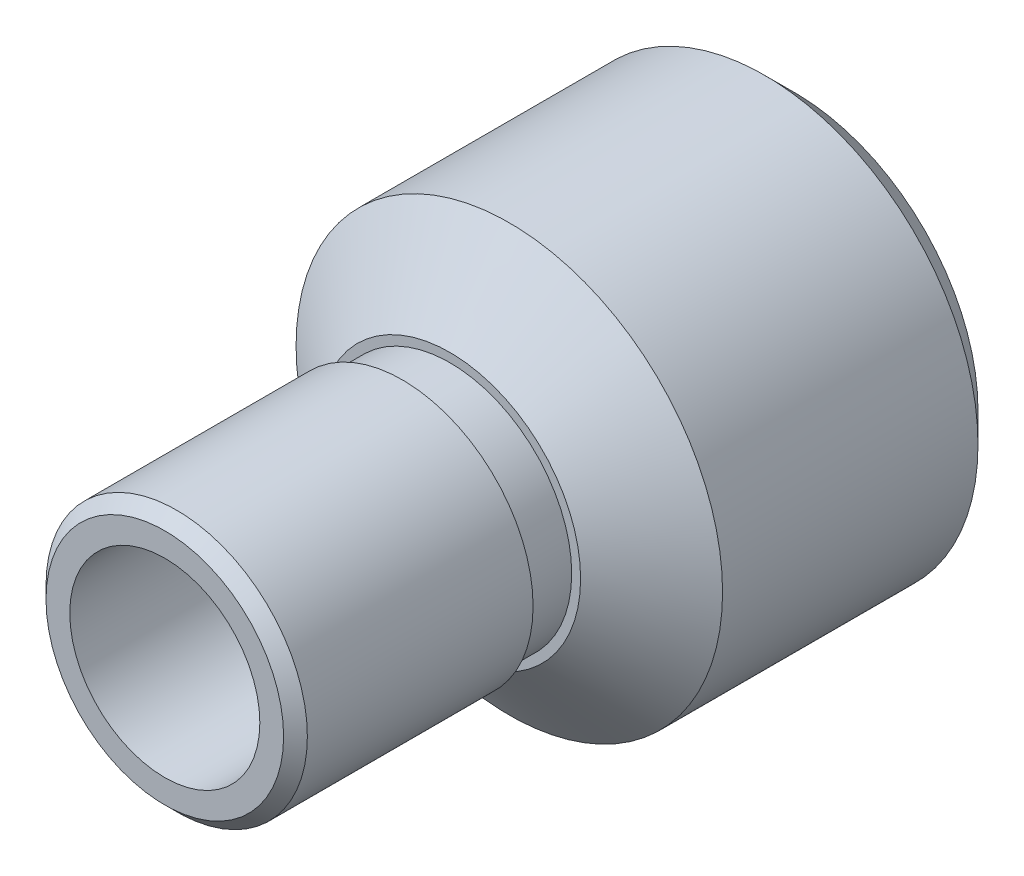
SolidWorks part; units mm, degrees
ref_plane "Front Plane" through (0, 0, 0) normal (0, 0, 1) x (1, 0, 0)
ref_plane "Top Plane" through (0, 0, 0) normal (0, 1, 0) x (1, 0, 0)
ref_plane "Right Plane" through (0, 0, 0) normal (1, 0, 0) x (0, 0, -1)
sketch "Sketch2" plane through (0, 0, 0) normal (1, 0, 0) x (0, 0, -1)
  line L0 (0, 11) -> (24, 11)
  line L1 (24, 11) -> (29, 17.95)
  line L2 (29, 17.95) -> (53, 17.95)
  line L3 (0, 11) -> (0, 0) construction
  line L4 (0, 0) -> (53, 0) construction
  line L5 (53, 0) -> (53, 17.95) construction
  line L6 (0, 8) -> (25.5374, 8)
  line L7 (25.5374, 8) -> (30.5374, 14.95)
  line L8 (30.5374, 14.95) -> (53, 14.95)
  line L9 (0, 11) -> (0, 8)
  line L10 (53, 17.95) -> (53, 14.95)
  dimension "D1" = 11
  dimension "D2" = 14.95
  dimension "D3" = 5
  dimension "D4" = 24
  dimension "D5" = 24
  dimension "D6" = 3
revolve "Revolve1" add sketch "Sketch2" angle 360 about L4
chamfer "Chamfer1" distance 2.5 angle 45 1 edges at (17.95, 0, -53)
sketch "Sketch3" plane through (0, 0, 0) normal (0, 0, 1) x (1, 0, 0)
  circle A0 centre (0, 0) radius 11 construction
  circle A1 centre (0, 0) radius 11
  circle A2 centre (0, 0) radius 10.25
  dimension "D1" = 0.75
extrude "Cut-Extrude1" cut sketch "Sketch3" against normal blind 4 from offset 20 offset against normal yes
sketch "Sketch4" plane through (0, 0, 0) normal (0, 0, 1) x (1, 0, 0)
  circle A0 centre (0, 0) radius 11.5
  circle A1 centre (0, 0) radius 11
  circle A2 centre (0, 0) radius 11
  dimension "D1" = 0
  dimension "D2" = 0.5
extrude "Boss-Extrude1" [suppressed] add sketch "Sketch4" against normal blind 5 from offset 5 offset against normal yes
chamfer "Chamfer2" distance 1 angle 45 1 edges at (11, 0, 0)
